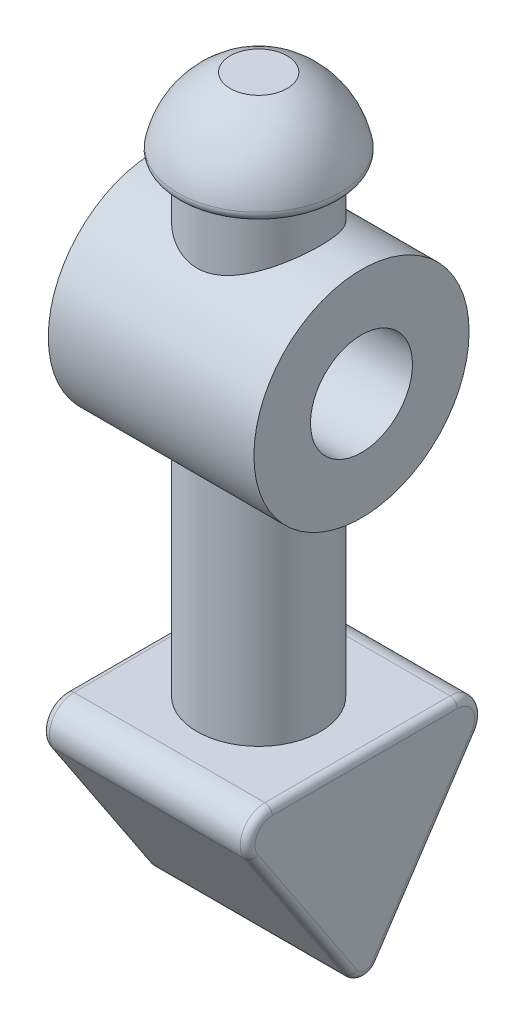
SolidWorks part; units mm, degrees
ref_plane "Front Plane" through (0, 0, 0) normal (0, 0, 1) x (1, 0, 0)
ref_plane "Top Plane" through (0, 0, 0) normal (0, 1, 0) x (1, 0, 0)
ref_plane "Right Plane" through (0, 0, 0) normal (1, 0, 0) x (0, 0, -1)
sketch "Sketch1" plane through (0, 0, 0) normal (1, 0, 0) x (0, 0, -1)
  circle A0 centre (0, 0) radius 16.6116
extrude "Boss-Extrude1" add sketch "Sketch1" along normal blind 31.75
ref_plane "Plane1" through (2.54, 0, 0) normal (1, 0, 0) x (0, 0, -1)
sketch "Sketch2" plane through (2.54, 0, 0) normal (1, 0, 0) x (0, 0, -1)
  circle A0 centre (0, 0) radius 11.6205
  circle A1 centre (0, 0) radius 16.6116
extrude "Cut-Extrude1" [suppressed] cut sketch "Sketch2" along normal blind 2.032
sketch "Sketch3" [suppressed] plane through (4.572, 0, 0) normal (-1, 0, 0) x (0, 0, 1)
  circle A0 centre (0, 0) radius 16.6116
  circle A1 centre (0, 0) radius 15.7988
ref_plane "Plane2" through (29.21, 0, 0) normal (1, 0, 0) x (0, 0, -1)
sketch "Sketch4" plane through (29.21, 0, 0) normal (1, 0, 0) x (0, 0, -1)
  circle A0 centre (0, 0) radius 11.6205
  circle A1 centre (0, 0) radius 16.6116
extrude "Cut-Extrude2" [suppressed] cut sketch "Sketch4" against normal blind 2.032
extrude "Cut-Extrude3" [suppressed] cut sketch "Sketch3" against normal up to surface (22.606 mm away)
sketch "Sketch5" plane through (0, 0, 0) normal (-1, 0, 0) x (0, 0, 1)
  circle A0 centre (0, 0) radius 7.874
  dimension "D1" = 15.748
extrude "Cut-Extrude4" cut sketch "Sketch5" against normal up to surface (31.75 mm away) up to face at (31.75, 0, -16.6116)
fillet "Fillet1" [suppressed] radius 1.651
fillet "Fillet2" [suppressed] radius 0.381
fillet "Fillet3" [suppressed] radius 0.762
ref_plane "Plane4" through (0, 16.6116, 0) normal (0, 1, 0) x (1, 0, 0)
ref_plane "Plane5" through (0, 23.6322, 0) normal (0, 1, 0) x (1, 0, 0)
sketch "Sketch7" plane through (0, 23.6322, 0) normal (0, 1, 0) x (1, 0, 0)
  line L0 (15.875, 15.7988) -> (15.875, -15.7988) construction
  circle A0 centre (15.875, 0) radius 9.525
  dimension "D1" = 19.05
extrude "Boss-Extrude2" add sketch "Sketch7" against normal blind 14.732
sketch "Sketch8" plane through (0, 23.6322, 0) normal (0, 1, 0) x (1, 0, 0)
  circle A0 centre (15.875, 0) radius 12.7
  dimension "D1" = 25.4
extrude "Boss-Extrude3" add sketch "Sketch8" along normal blind 11.43
sketch "Sketch9" plane through (0, 35.0622, 0) normal (0, 1, 0) x (1, 0, 0)
  circle A0 centre (15.875, 0) radius 6.858
sketch "Sketch10" plane through (0, 0, 0) normal (0, 0, 1) x (1, 0, 0)
  line L0 (11.4874, 35.0622) -> (3.175, 35.0622)
  line L1 (3.175, 35.0622) -> (3.175, 23.6322)
  line L2 (15.875, 35.0622) -> (15.875, 19.0536) construction
  line L3 (3.175, 35.0622) -> (3.175, 23.6322) construction
  line L4 (3.175, 23.6322) -> (28.575, 23.6322) construction
  arc A0 (11.4874, 35.0622) -> (3.175, 23.6322) centre (16.76, 22.4901) ccw
  point P5 (0, 0)
  point P7 (0, 0)
  point P10 (3.175, 23.6322)
  dimension "D1" = 0
revolve "Cut-Revolve1" cut sketch "Sketch10" angle 360 about L2
fillet "Fillet5" radius 1.27 1 edges at (15.875, 23.6322, 12.7)
sketch "Sketch11" plane through (0, 0, 0) normal (0, 0, 1) x (1, 0, 0)
  line L0 (15.875, 35.0622) -> (15.875, -72.8878) construction
ref_plane "Plane6" through (15.875, 0, 0) normal (1, 0, 0) x (0, 0, -1)
sketch "Sketch12" plane through (15.875, 0, 0) normal (1, 0, 0) x (0, 0, -1)
  line L0 (0.5127, -78.534) -> (0.5127, -31.0337) construction
  line L1 (2.6291, -77.3984) -> (7.3131, -70.3406)
  line L2 (-13.7709, -48.3616) -> (14.7981, -48.3616)
  line L3 (-22.9, -16.6116) -> (22.7687, -16.6116) construction
  line L5 (-16.9456, -54.2782) -> (-6.2871, -70.3406)
  line L8 (17.9726, -54.2784) -> (7.3131, -70.3406)
  line L9 (-6.2871, -70.3406) -> (-1.6037, -77.3984)
  arc A0 (17.9726, -54.2784) -> (14.7981, -48.3616) centre (14.7981, -52.1716) ccw
  arc A1 (2.6291, -77.3984) -> (-1.6037, -77.3984) centre (0.5127, -75.994) cw
  arc A2 (-16.9456, -54.2782) -> (-13.7709, -48.3616) centre (-13.7709, -52.1716) cw
  circle A3 centre (0, 0) radius 16.6116 construction
  dimension "D1" = 2.54
  dimension "D2" = 3.81
  dimension "D5" = 7.62
  dimension "D3" = 33.567
  dimension "D4" = 33.57
  dimension "D6" = 28.569
  dimension "D7" = 31.75
extrude "Boss-Extrude4" add sketch "Sketch12" along normal blind 15.875 and the other way blind 15.875 separate body
ref_plane "Plane7" through (0, -16.6116, 0) normal (0, -1, 0) x (-1, 0, 0)
sketch "Sketch13" plane through (0, -16.6116, 0) normal (0, -1, 0) x (-1, 0, 0)
  circle A0 centre (-15.875, 0) radius 9.525
  dimension "D1" = 19.05
extrude "Boss-Extrude5" add sketch "Sketch13" along normal blind 31.75 and the other way blind 3.81
ref_plane "Plane8" through (0, 0, -11.43) normal (0, 0, 1) x (1, 0, 0)
ref_plane "Plane9" through (0, 0, 11.43) normal (0, 0, 1) x (1, 0, 0)
ref_plane "Plane11" [suppressed] through (0, 0, 15.7988) normal (0, 0, 1) x (1, 0, 0)
ref_plane "Plane12" [suppressed] through (0, 0, -15.7988) normal (0, 0, -1) x (-1, 0, 0)
fillet "Fillet6" radius 1.143 12 edges at (0, -65.8384, -10.3009) (31.75, -65.8384, -10.3009) (0, -78.534, -0.5127) (0, -65.8383, 9.2746) (0, -50.3702, 17.1282) (0, -48.3616, -0.5136) (0, -50.3703, -18.1554) (31.75, -78.534, -0.5127) (31.75, -65.8383, 9.2746) (31.75, -50.3702, 17.1282) (31.75, -48.3616, -0.5136) (31.75, -50.3703, -18.1554)
ref_plane "Plane14" through (6.35, 0, 0) normal (1, 0, 0) x (0, 0, -1)
